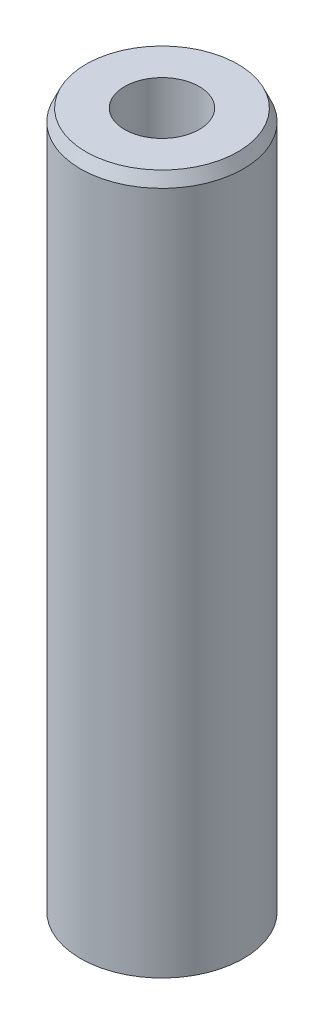
SolidWorks part; units mm, degrees
ref_plane "Front Plane" through (0, 0, 0) normal (0, 0, 1) x (1, 0, 0)
ref_plane "Top Plane" through (0, 0, 0) normal (0, 1, 0) x (1, 0, 0)
ref_plane "Right Plane" through (0, 0, 0) normal (1, 0, 0) x (0, 0, -1)
sketch "Sketch1" plane through (0, 0, 0) normal (0, 1, 0) x (1, 0, 0)
  circle A0 centre (0, 0) radius 20
  dimension "SHAFT_OD" = 40
extrude "Boss-Extrude1" add sketch "Sketch1" along normal blind 172.1576
sketch "Sketch2" plane through (0, 0, 0) normal (0, 1, 0) x (1, 0, 0)
  circle A0 centre (0, 0) radius 9.1544
  dimension "BORE_D" = 18.3089
extrude "Cut-Extrude1" cut sketch "Sketch2" along normal through all
chamfer "Chamfer1" distance 2.943 angle 24.712 2 edges at (0, 172.1576, 20) (0, 0, 20) first distance on face at (0, 172.1576, 20) first distance on face at (0, 0, 9.1544)
